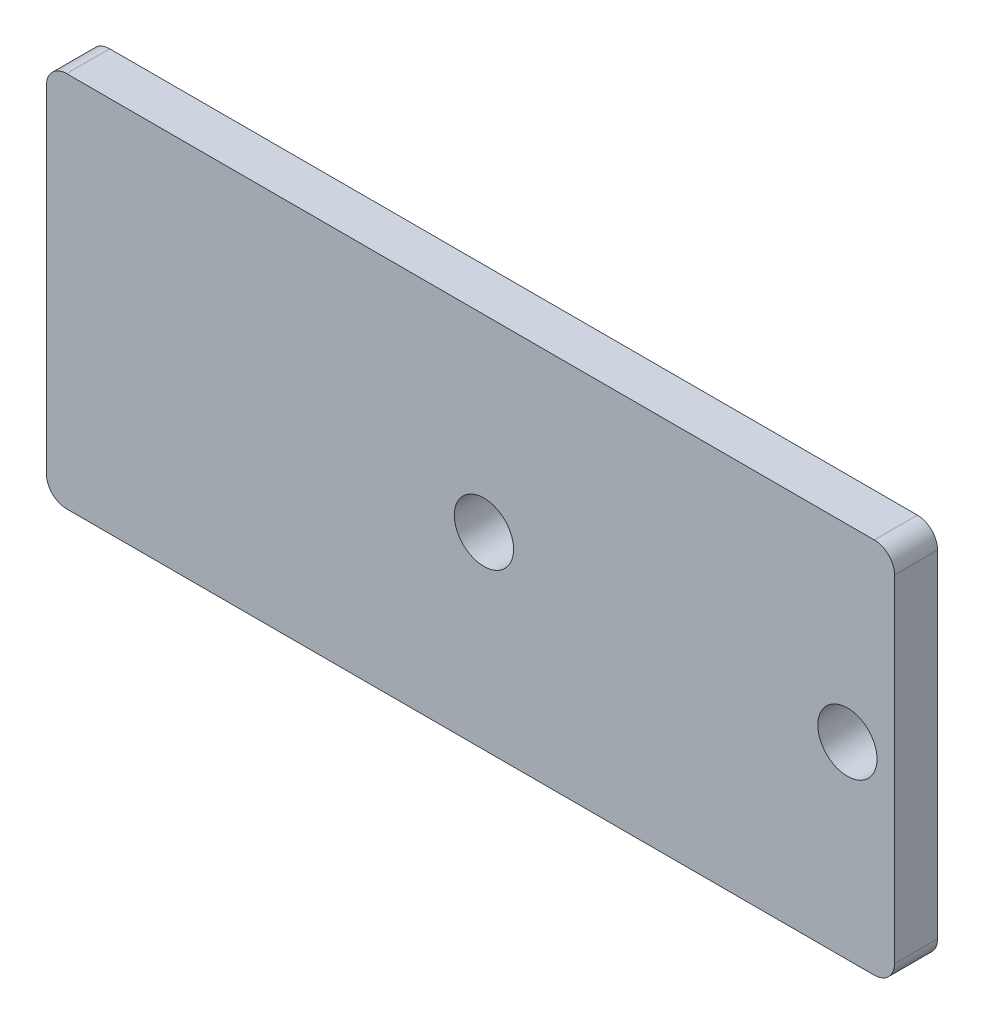
SolidWorks part; units mm, degrees
material "FR4_stuffedProtoboard"
ref_plane "Front Plane" through (0, 0, 0) normal (0, 0, 1) x (1, 0, 0)
ref_plane "Top Plane" through (0, 0, 0) normal (0, 1, 0) x (1, 0, 0)
ref_plane "Right Plane" through (0, 0, 0) normal (1, 0, 0) x (0, 0, -1)
sketch "Model" plane through (0, 0, 0) normal (0, 0, 1) x (1, 0, 0)
  line L0 (-15, -7) -> (15, -7)
  line L1 (15.75, -6.25) -> (15.75, 6.25)
  line L2 (15, 7) -> (-15, 7)
  line L3 (-15.75, 6.25) -> (-15.75, -6.25)
  arc A0 (15.75, 6.25) -> (15, 7) centre (15, 6.25) ccw
  arc A1 (15, -7) -> (15.75, -6.25) centre (15, -6.25) ccw
  arc A2 (-15.75, -6.25) -> (-15, -7) centre (-15, -6.25) ccw
  arc A3 (-15, 7) -> (-15.75, 6.25) centre (-15, 6.25) ccw
  circle A4 centre (0.5, 0) radius 1.1
  circle A5 centre (14, 0) radius 1.1
  point P23 (0, 7)
  point P24 (15.75, 0)
  dimension "D3" = 0.75
  dimension "D7" = 0.75
  dimension "D8" = 2.2
  dimension "D9" = 2.2
  dimension "D1" = 30
  dimension "D2" = 12.5
  dimension "D4" = 6.25
  dimension "D5" = 13.5
  dimension "D6" = 1.75
  dimension "D10" = 0.75
extrude "Boss-Extrude1" add sketch "Model" along normal mid plane 1.6
sketch "Sketch1" plane through (0, 0, -0.8) normal (0, 0, 1) x (1, 0, 0)
  line L0 (15, 7) -> (-15, 7) construction
  line L1 (-13.75, 5) -> (-3.75, 5)
  line L2 (-13.75, 5) -> (-13.75, -5)
  line L3 (-13.75, -5) -> (-3.75, -5)
  line L4 (-3.75, 5) -> (-3.75, -5)
  line L5 (-15.75, 6.25) -> (-15.75, -6.25) construction
  dimension "D1" = 2
  dimension "D2" = 2
  dimension "D3" = 10
  dimension "D4" = 10
